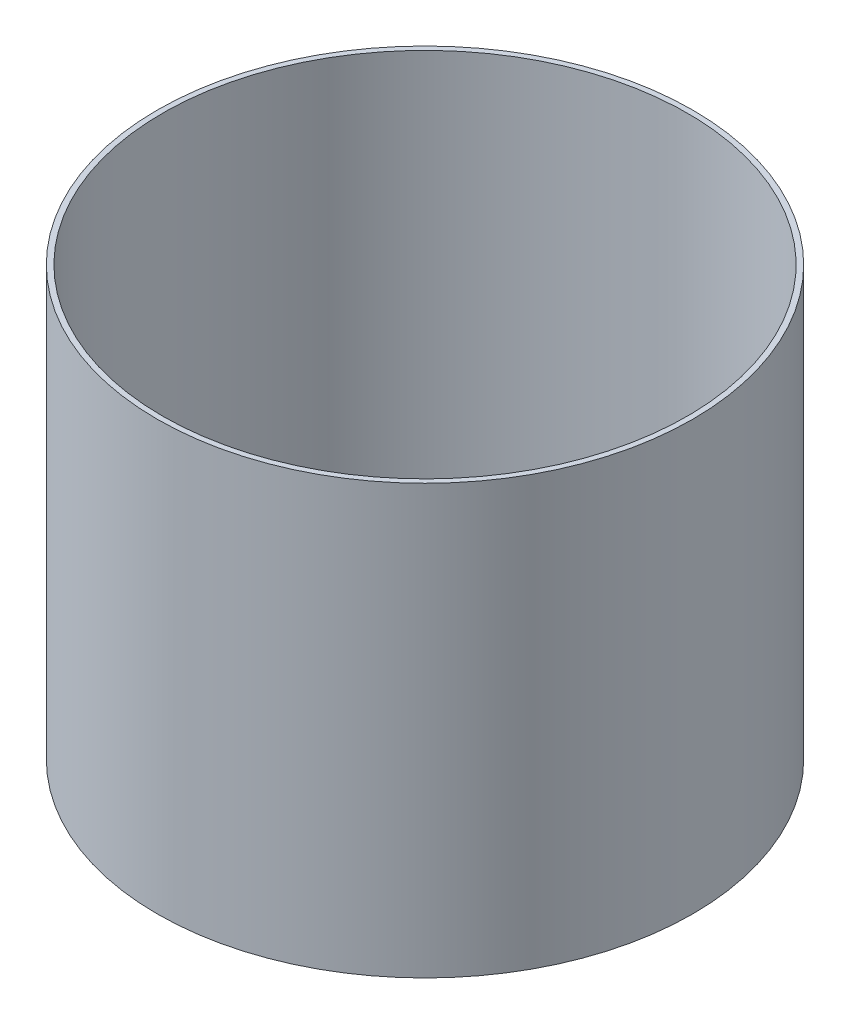
SolidWorks part; units mm, degrees
ref_plane "Front" through (0, 0, 0) normal (0, 0, 1) x (1, 0, 0)
ref_plane "Top" through (0, 0, 0) normal (0, 1, 0) x (1, 0, 0)
ref_plane "Right" through (0, 0, 0) normal (1, 0, 0) x (0, 0, -1)
sketch "Sketch1" plane through (0, 0, 0) normal (0, 1, 0) x (1, 0, 0)
  circle A0 centre (0, 0) radius 127
  dimension "D1" = 254
extrude "Boss-Extrude1" add sketch "Sketch1" along normal blind 203.2
shell "Shell1" thickness 2.54 removed face at (0, 203.2, 127)
